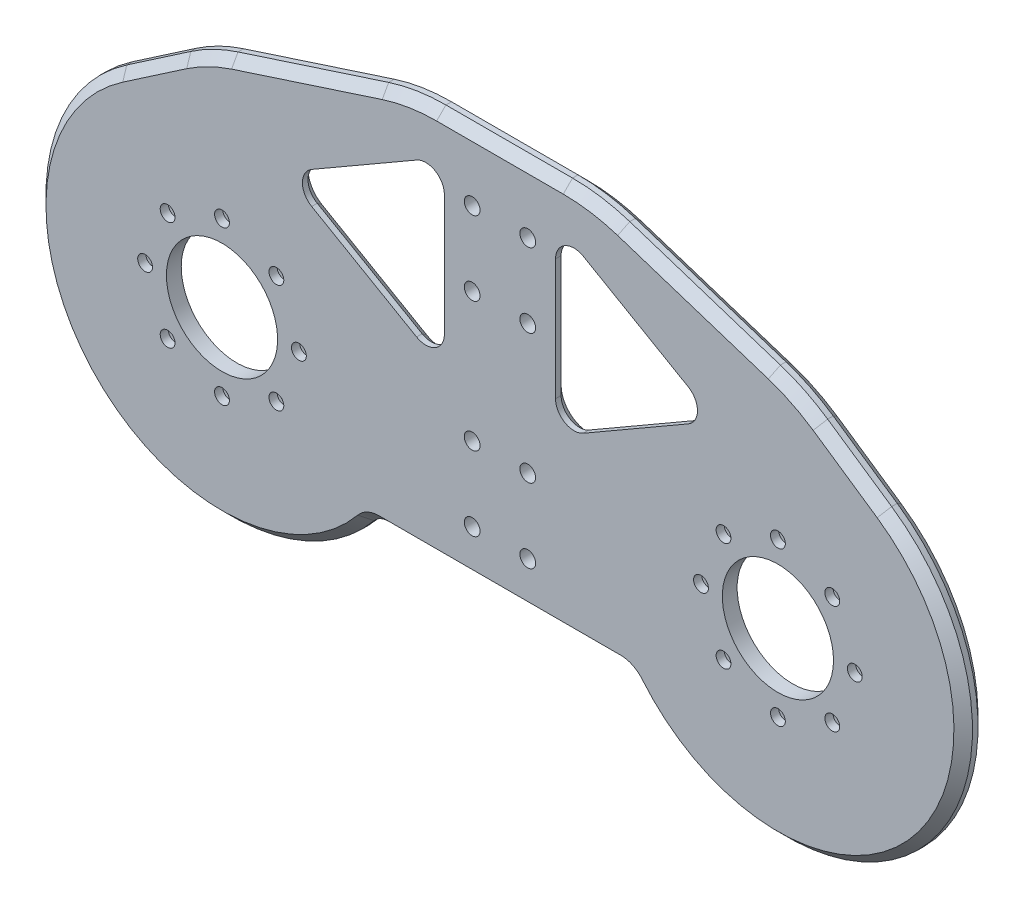
SolidWorks part; units mm, degrees
material "6061 合金"
ref_plane "前视基准面" through (0, 0, 0) normal (0, 0, 1) x (1, 0, 0)
ref_plane "上视基准面" through (0, 0, 0) normal (0, 1, 0) x (1, 0, 0)
ref_plane "右视基准面" through (0, 0, 0) normal (1, 0, 0) x (0, 0, -1)
other "Configuration Table"
sketch "草图1" plane through (0, 0, 0) normal (0, 0, 1) x (1, 0, 0)
  line L0 (0, 0) -> (0, 250) construction
  line L1 (0, 250) -> (769.4209, 0)
  line L3 (769.4209, 0) -> (0, 0)
  line L4 (-50, 404.7785) -> (-50, -103.66) construction
  line L5 (-869.4209, 0) -> (-100, 0)
  line L6 (-100, 250) -> (-869.4209, 0)
  line L7 (-100, 0) -> (-100, 250) construction
  line L8 (-100, 250) -> (0, 250)
  line L9 (-100, 0) -> (0, 0)
  circle A0 centre (100, 100) radius 85 construction
  circle A1 centre (100, 100) radius 30
  circle A2 centre (-200, 100) radius 85 construction
  circle A3 centre (-200, 100) radius 30
  dimension "D1" = 170
  dimension "D4" = 60
  dimension "D2" = 150
  dimension "D3" = 72
  dimension "D5" = 250
  dimension "D6" = 100
  dimension "D7" = 50
extrude "凸台-拉伸1" add sketch "草图1" along normal blind 8
sketch "草图8" plane through (0, 0, 8) normal (0, 0, 1) x (1, 0, 0)
  line L0 (100, 100) -> (100, 171.8517) construction
  line L1 (-50, 311.6242) -> (-50, -58.5513) construction
  line L2 (-200, 100) -> (-200, 171.8517) construction
  circle A0 centre (100, 100) radius 41.5 construction
  circle A1 centre (100, 141.5) radius 2.25
  circle A2 centre (129.3449, 129.3449) radius 2.25
  circle A3 centre (141.5, 100) radius 2.25
  circle A4 centre (129.3449, 70.6551) radius 2.25
  circle A5 centre (100, 58.5) radius 2.25
  circle A6 centre (70.6551, 70.6551) radius 2.25
  circle A7 centre (58.5, 100) radius 2.25
  circle A8 centre (70.6551, 129.3449) radius 2.25
  circle A9 centre (100, 100) radius 30 construction
  circle A10 centre (-200, 100) radius 30 construction
  circle A11 centre (-200, 100) radius 41.5 construction
  circle A12 centre (-170.6551, 129.3449) radius 2.25
  circle A13 centre (-158.5, 100) radius 2.25
  circle A14 centre (-170.6551, 70.6551) radius 2.25
  circle A15 centre (-200, 58.5) radius 2.25
  circle A16 centre (-229.3449, 70.6551) radius 2.25
  circle A17 centre (-241.5, 100) radius 2.25
  circle A18 centre (-229.3449, 129.3449) radius 2.25
  circle A19 centre (-200, 141.5) radius 2.25
  point P22 (100, 100)
  point P46 (-200, 100)
  dimension "D1" = 83
  dimension "D2" = 4.5
  dimension "D3" = 8
extrude "切除-拉伸5" cut sketch "草图8" against normal through all both and the other way through all
sketch "草图9" plane through (0, 0, 8) normal (0, 0, 1) x (1, 0, 0)
  line L0 (-50, 330.1155) -> (-50, -36.3961) construction
  circle A0 centre (-200, 100) radius 41.5 construction
  circle A1 centre (-200, 141.5) radius 4
  circle A2 centre (-170.6551, 129.3449) radius 4
  circle A3 centre (-158.5, 100) radius 4
  circle A4 centre (-170.6551, 70.6551) radius 4
  circle A5 centre (-200, 58.5) radius 4
  circle A6 centre (-229.3449, 70.6551) radius 4
  circle A7 centre (-241.5, 100) radius 4
  circle A8 centre (-229.3449, 129.3449) radius 4
  circle A9 centre (100, 100) radius 30 construction
  circle A10 centre (-200, 100) radius 30 construction
  circle A11 centre (100, 100) radius 41.5 construction
  circle A12 centre (129.3449, 129.3449) radius 4
  circle A13 centre (141.5, 100) radius 4
  circle A14 centre (129.3449, 70.6551) radius 4
  circle A15 centre (100, 58.5) radius 4
  circle A16 centre (70.6551, 70.6551) radius 4
  circle A17 centre (58.5, 100) radius 4
  circle A18 centre (70.6551, 129.3449) radius 4
  circle A19 centre (100, 141.5) radius 4
  point P22 (-200, 100)
  point P45 (100, 100)
  dimension "D1" = 8
  dimension "D2" = 8
extrude "切除-拉伸6" cut sketch "草图9" against normal blind 4.4
fillet "圆角1" radius 100 2 edges at (-869.4209, 0, 4) (769.4209, 0, 4)
sketch "草图12" plane through (0, 0, 0) normal (0, 0, -1) x (-1, 0, 0)
  line L0 (50, 285.9765) -> (50, -67.6003) construction
  line L1 (238.0457, 0) -> (-138.0457, 0) construction
  line L3 (-20, 40) -> (120, 40)
  line L6 (200, 0) -> (-100, 0)
  arc A0 (120, 40) -> (200, 0) centre (200, 100) ccw
  circle A2 centre (200, 100) radius 30 construction
  circle A3 centre (-100, 100) radius 30 construction
  arc A7 (-100, 0) -> (-20, 40) centre (-100, 100) ccw
  dimension "D1" = 40
extrude "切除-拉伸7" cut sketch "草图12" against normal blind 83
sketch "草图13" plane through (0, 0, 8) normal (0, 0, 1) x (1, 0, 0)
  line L0 (-238.0457, 0) -> (-200, 0) construction
  line L1 (-238.0457, 0) -> (-200, 0)
  line L2 (-50, 304.265) -> (-50, -26.0703) construction
  line L3 (-210, 214.2588) -> (-256.3883, 182.5854)
  line L4 (-100, 250) -> (-268.9474, 195.1057) construction
  line L5 (-210, 214.2588) -> (-268.9474, 195.1057)
  line L6 (110, 214.2588) -> (168.9474, 195.1057)
  line L7 (110, 214.2588) -> (156.3883, 182.5854)
  line L8 (138.0457, 0) -> (100, 0)
  arc A0 (-256.3883, 182.5854) -> (-200, 0) centre (-200, 100) ccw
  circle A1 centre (100, 100) radius 30 construction
  circle A2 centre (-200, 100) radius 30 construction
  arc A3 (-268.9474, 195.1057) -> (-238.0457, 0) centre (-238.0457, 100) ccw construction
  arc A4 (-268.9474, 195.1057) -> (-238.0457, 0) centre (-238.0457, 100) ccw
  arc A5 (168.9474, 195.1057) -> (138.0457, 0) centre (138.0457, 100) cw
  arc A6 (156.3883, 182.5854) -> (100, 0) centre (100, 100) cw
  dimension "D1" = 160
extrude "切除-拉伸8" cut sketch "草图13" against normal blind 83
fillet "圆角3" radius 100 4 edges at (110, 214.2588, 4) (0, 250, 4) (-100, 250, 4) (-210, 214.2588, 4)
fillet "圆角4" radius 10 2 edges at (20, 40, 4) (-120, 40, 4)
sketch "草图14" plane through (0, 0, 8) normal (0, 0, 1) x (1, 0, 0)
  line L0 (-50, 283.8941) -> (-50, -28.6031) construction
  line L1 (-115.1472, 40) -> (15.1472, 40) construction
  circle A0 centre (-200, 100) radius 30 construction
  circle A1 centre (100, 100) radius 30 construction
  circle A2 centre (-35, 65) radius 4.25
  circle A3 centre (-35, 105) radius 4.25
  circle A4 centre (-35, 175) radius 4.25
  circle A5 centre (-35, 215) radius 4.25
  circle A6 centre (-65, 215) radius 4.25
  circle A7 centre (-65, 175) radius 4.25
  circle A8 centre (-65, 105) radius 4.25
  circle A9 centre (-65, 65) radius 4.25
  dimension "D6" = 8.5
  dimension "D1" = 40
  dimension "D2" = 15
  dimension "D3" = 40
  dimension "D4" = 70
  dimension "D5" = 15
  dimension "D7" = 25
extrude "切除-拉伸9" cut sketch "草图14" against normal blind 83
sketch "草图15" plane through (0, 0, 0) normal (0, 0, -1) x (-1, 0, 0)
  line L0 (50, 291.1692) -> (50, -23.3122) construction
  line L1 (55, 50) -> (128.193, 50)
  line L2 (55, 240) -> (98.4162, 240)
  line L3 (98.4162, 240) -> (197.0868, 207.94)
  line L4 (197.0868, 207.94) -> (249.3398, 172.2623)
  line L5 (115.1472, 40) -> (-15.1472, 40) construction
  line L6 (15.8384, 250) -> (84.1616, 250) construction
  line L7 (115.0633, 245.1057) -> (196.3588, 218.6911) construction
  line L8 (221.8454, 206.1709) -> (256.3883, 182.5854) construction
  line L9 (55, 240) -> (55, 50)
  line L10 (45, 240) -> (45, 50)
  line L11 (-97.0868, 207.94) -> (-149.3398, 172.2623)
  line L12 (1.5838, 240) -> (-97.0868, 207.94)
  line L13 (45, 240) -> (1.5838, 240)
  line L14 (45, 50) -> (-28.193, 50)
  line L21 (-15.0633, 245.1057) -> (-96.3588, 218.6911)
  line L22 (-121.8454, 206.1709) -> (-156.3883, 182.5854)
  line L23 (-15.1472, 40) -> (115.1472, 40)
  line L24 (256.3883, 182.5854) -> (221.8454, 206.1709)
  line L25 (196.3588, 218.6911) -> (115.0633, 245.1057)
  line L26 (84.1616, 250) -> (15.8384, 250)
  line L27 (-15.0633, 245.1057) -> (-96.3588, 218.6911)
  line L28 (-121.8454, 206.1709) -> (-156.3883, 182.5854)
  line L29 (-15.1472, 40) -> (115.1472, 40)
  line L30 (256.3883, 182.5854) -> (221.8454, 206.1709)
  line L31 (196.3588, 218.6911) -> (115.0633, 245.1057)
  line L32 (84.1616, 250) -> (15.8384, 250)
  circle A0 centre (200, 100) radius 87.5 construction
  circle A1 centre (200, 100) radius 30 construction
  circle A2 centre (-100, 100) radius 30 construction
  arc A3 (128.193, 50) -> (249.3398, 172.2623) centre (200, 100) ccw
  circle A4 centre (-100, 100) radius 87.5 construction
  arc A5 (-28.193, 50) -> (-149.3398, 172.2623) centre (-100, 100) cw
  arc A14 (-96.3588, 218.6911) -> (-121.8454, 206.1709) centre (-65.4571, 123.5855) ccw
  arc A15 (-156.3883, 182.5854) -> (-22.8611, 36.3636) centre (-100, 100) ccw
  arc A16 (-15.1472, 40) -> (-22.8611, 36.3636) centre (-15.1472, 30) ccw
  arc A17 (122.8611, 36.3636) -> (115.1472, 40) centre (115.1472, 30) ccw
  arc A18 (122.8611, 36.3636) -> (256.3883, 182.5854) centre (200, 100) ccw
  arc A19 (221.8454, 206.1709) -> (196.3588, 218.6911) centre (165.4571, 123.5855) ccw
  arc A20 (115.0633, 245.1057) -> (84.1616, 250) centre (84.1616, 150) ccw
  arc A21 (15.8384, 250) -> (-15.0633, 245.1057) centre (15.8384, 150) ccw
  arc A22 (-96.3588, 218.6911) -> (-121.8454, 206.1709) centre (-65.4571, 123.5855) ccw
  arc A23 (-156.3883, 182.5854) -> (-22.8611, 36.3636) centre (-100, 100) ccw
  arc A24 (-15.1472, 40) -> (-22.8611, 36.3636) centre (-15.1472, 30) ccw
  arc A25 (122.8611, 36.3636) -> (115.1472, 40) centre (115.1472, 30) ccw
  arc A26 (122.8611, 36.3636) -> (256.3883, 182.5854) centre (200, 100) ccw
  arc A27 (221.8454, 206.1709) -> (196.3588, 218.6911) centre (165.4571, 123.5855) ccw
  arc A28 (115.0633, 245.1057) -> (84.1616, 250) centre (84.1616, 150) ccw
  arc A29 (15.8384, 250) -> (-15.0633, 245.1057) centre (15.8384, 150) ccw
  dimension "D1" = 175
  dimension "D2" = 10
  dimension "D3" = 10
  dimension "D4" = 10
  dimension "D5" = 5
  dimension "D6" = 0
extrude "凸台-拉伸2" add sketch "草图15" along normal blind 5
sketch "草图16" plane through (0, 0, 0) normal (0, 0, -1) x (-1, 0, 0)
  line L0 (80, 230) -> (80, 130)
  line L1 (80, 130) -> (166.6025, 180)
  line L2 (166.6025, 180) -> (80, 230)
  line L3 (50, 302.4124) -> (50, -31.91) construction
  line L4 (84.1616, 250) -> (15.8384, 250) construction
  line L5 (-66.6025, 180) -> (20, 230)
  line L6 (20, 130) -> (-66.6025, 180)
  line L7 (20, 230) -> (20, 130)
  circle A0 centre (200, 100) radius 30 construction
  circle A1 centre (-100, 100) radius 30 construction
  dimension "D1" = 30
  dimension "D2" = 20
  dimension "D3" = 100
  dimension "D4" = 100
  dimension "D5" = 100
extrude "切除-拉伸10" cut sketch "草图16" against normal blind 69
fillet "圆角5" radius 10 16 edges at (97.0868, 207.94, -2.5) (-1.5838, 240, -2.5) (28.193, 50, -2.5) (-45, 50, -2.5) (-45, 240, -2.5) (-98.4162, 240, -2.5) (-197.0868, 207.94, -2.5) (-128.193, 50, -2.5) (-55, 50, -2.5) (-55, 240, -2.5) (-166.6025, 180, 4) (-80, 130, 4) (-80, 230, 4) (-20, 230, 4) (66.6025, 180, 4) (-20, 130, 4)
chamfer "倒角1" distance 5 angle 45 28 edges at (-119.4112, 39.0453, 8) (-50, 40, 8) (-273.8434, 32.5674, 8) (19.4112, 39.0453, 8) (-239.1169, 194.3782, 8) (173.8434, 32.5674, 8) (-209.5488, 213.3403, 8) (139.1169, 194.3782, 8) (-155.711, 231.8984, 8) (109.5488, 213.3403, 8) (-99.805, 248.7688, 8) (55.711, 231.8984, 8) (-50, 250, 8) (-0.195, 248.7688, 8) (-50, 40, -5) (-119.4112, 39.0453, -5) (19.4112, 39.0453, -5) (-273.8434, 32.5674, -5) (173.8434, 32.5674, -5) (-239.1169, 194.3782, -5) (139.1169, 194.3782, -5) (-209.5488, 213.3403, -5) (109.5488, 213.3403, -5) (-155.711, 231.8984, -5) (55.711, 231.8984, -5) (-99.805, 248.7688, -5) (-0.195, 248.7688, -5) (-50, 250, -5)
chamfer "倒角2" distance 5 angle 45 12 edges at (-85, 221.3397, 0) (-80, 180, 0) (-123.3013, 205, 0) (-85, 138.6603, 0) (-156.6025, 180, 0) (-123.3013, 155, 0) (-15, 221.3397, 0) (23.3013, 205, 0) (-20, 180, 0) (56.6025, 180, 0) (-15, 138.6603, 0) (23.3013, 155, 0)
